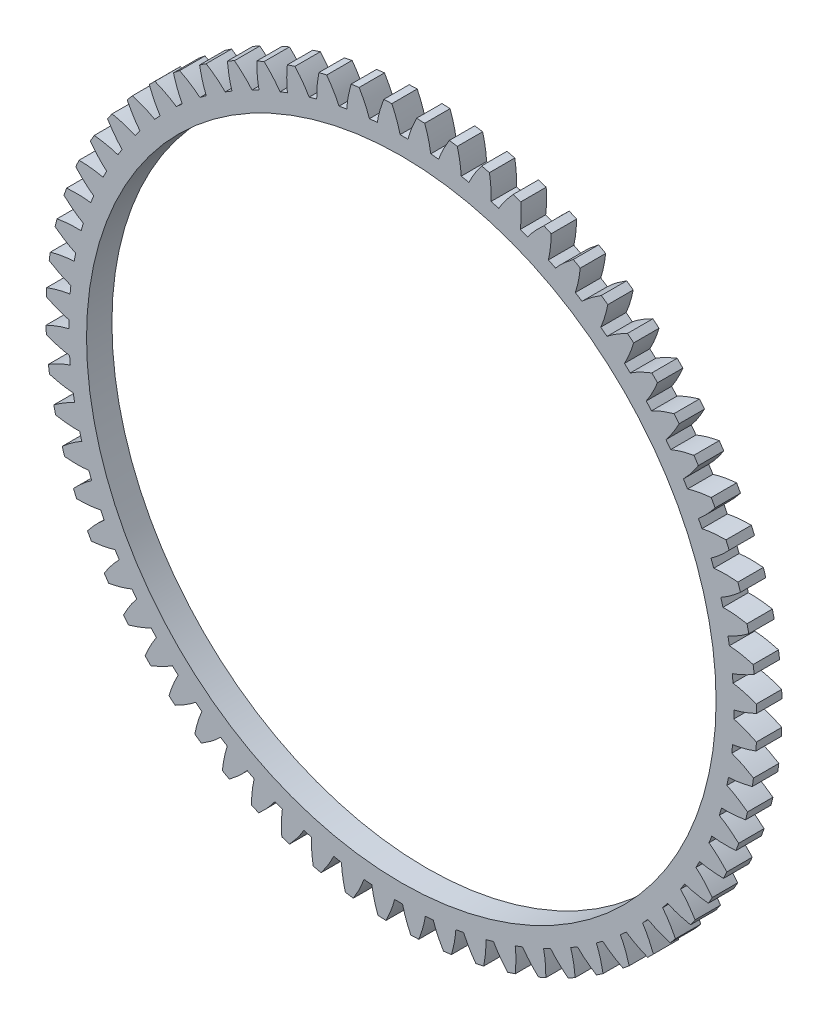
SolidWorks part; units mm, degrees
ref_plane "前视基准面" through (0, 0, 0) normal (0, 0, 1) x (1, 0, 0)
ref_plane "上视基准面" through (0, 0, 0) normal (0, 1, 0) x (1, 0, 0)
ref_plane "右视基准面" through (0, 0, 0) normal (1, 0, 0) x (0, 0, -1)
sketch "草图1" plane through (0, 0, 0) normal (0, 0, 1) x (1, 0, 0)
  circle A0 centre (0, 0) radius 32.75
  circle A1 centre (0, 0) radius 31
  dimension "D1" = 65.5
  dimension "D2" = 62
extrude "凸台-拉伸1" add sketch "草图1" along normal blind 2.5
sketch "草图2" plane through (0, 0, 0) normal (0, 0, 1) x (1, 0, 0)
  arc A0 (34.9574, 1.7254) -> (34.9875, 0.9341) centre (0, 0) cw
  arc A1 (31.8573, 2.4261) -> (31.9495, 0) centre (0, 0) cw
  spline S0 degree 3 poles (34.9875, 0.9341) (34.6576, 0.7759) (34.1574, 0.5589) (33.4773, 0.3186) (32.8061, 0.1215) (32.2942, 0.0196) (31.9495, 0) knots 0 0 0 0 0.343518 0.511474 0.676893 1 1 1 1
  spline S1 degree 3 poles (34.9574, 1.7254) (34.6165, 1.8581) (34.1012, 2.0365) (33.4048, 2.2244) (32.7206, 2.37) (32.2024, 2.4327) (31.8573, 2.4261) knots 0 0 0 0 0.343518 0.511474 0.676893 1 1 1 1
extrude "凸台-拉伸2" add sketch "草图2" along normal blind 2.5
pattern_circular "阵列(圆周)1" count 68 over 360 about axis through (0, 0, 2.5) along (0, 0, -1) of "凸台-拉伸2"
